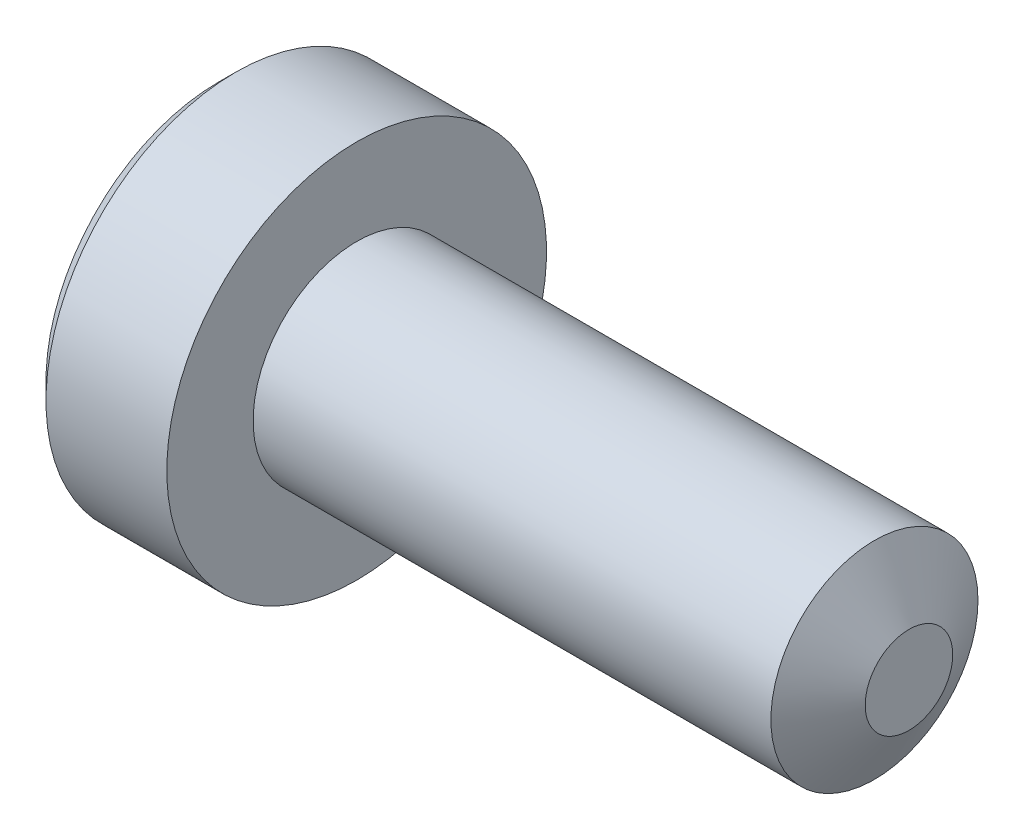
SolidWorks part; units mm, degrees
ref_plane "Front Plane" through (0, 0, 0) normal (0, 0, 1) x (1, 0, 0)
ref_plane "Top Plane" through (0, 0, 0) normal (0, 1, 0) x (1, 0, 0)
ref_plane "Right Plane" through (0, 0, 0) normal (1, 0, 0) x (0, 0, -1)
sketch "Sketch1" plane through (0, 0, 0) normal (0, 0, 1) x (1, 0, 0)
  line L0 (4, 0) -> (-4, 0) construction
  line L1 (4, 1.5) -> (4, -1.5) construction
  line L2 (-4, 2.75) -> (-4, -2.75) construction
  line L3 (-4, 2.75) -> (-5.75, 2.75) construction
  line L4 (-5.75, 2.75) -> (-6, 2.5) construction
  line L5 (-6, 2.5) -> (-6, -2.5) construction
  line L6 (-6, -2.5) -> (-5.75, -2.75) construction
  line L7 (-5.75, -2.75) -> (-4, -2.75) construction
  point P7 (-4.38, 0)
  point P12 (2, -1.5)
  dimension "D1" = 45
  dimension "Dec." = 3
  dimension "Length" = 8
  dimension "Head Dia" = 5.5
  dimension "Head Height" = 2
  dimension "Hex Depth" = 1.62
  dimension "Chamfer" = 0.25
  dimension "D2" = 2
ref_plane "Plane1" through (4, 0, 0) normal (1, 0, 0) x (0, 0, -1)
ref_plane "Plane2" through (-6, 0, 0) normal (1, 0, 0) x (0, 0, -1)
sketch "Sketch2" plane through (4, 0, 0) normal (1, 0, 0) x (0, 0, -1)
  circle A0 centre (0, 0) radius 1.5
extrude "Boss-Extrude1" add sketch "Sketch2" against normal up to vertex (8 mm away) up to point (-4, 0, 0)
sketch "Sketch3" plane through (4, 0, 0) normal (1, 0, 0) x (0, 0, -1)
  circle A0 centre (0, 0) radius 1.5 construction
  circle A1 centre (0, 0) radius 1.5
curve "Helix/Spiral1" pitch 0.5 height 8.5 radius 1.5 centre (4, 0, 0) axis (-1, 0, 0) start towards (0, 1, 0) parameters "Pitch"=0.5
chamfer "Chamfer1" distance 0.375 angle 45 1 edges at (4, 0, -1.5)
sketch "Sketch5" plane through (0, 0, 0) normal (0, 0, 1) x (1, 0, 0)
  line L0 (3.7813, 1.5) -> (4.2188, 1.5)
  line L1 (4.2188, 1.5) -> (4.0313, 1.1752)
  line L2 (4.0313, 1.1752) -> (3.9688, 1.1752)
  line L3 (3.9688, 1.1752) -> (3.7813, 1.5)
  line L4 (4, 1.1752) -> (4, 1.5) construction
  line L5 (3.875, 1.3376) -> (4.125, 1.3376) construction
  dimension "D1" = 60
  dimension "D2" = 0.25
  dimension "D3" = 0.0625
sweep "Cut-Sweep1" cut profiles "Sketch5" path "Helix/Spiral1" align with end faces yes
sketch "Sketch4" plane through (-6, 0, 0) normal (1, 0, 0) x (0, 0, -1)
  line L0 (-2.75, 0.7937) -> (2.75, 0.7937) construction
  line L1 (0, 1.1547) -> (-1, 0.5774)
  line L2 (-1, 0.5774) -> (-1, -0.5774)
  line L3 (-1, -0.5774) -> (0, -1.1547)
  line L4 (0, -1.1547) -> (1, -0.5774)
  line L5 (1, -0.5774) -> (1, 0.5774)
  line L6 (1, 0.5774) -> (0, 1.1547)
  line L7 (0, 0) -> (0, 0.7937) construction
  circle A0 centre (0, 0) radius 1 construction
  dimension "Hex Size" = 2
  dimension "D1" = 5.5
  dimension "D2" = 0.7937
sketch "Sketch6" plane through (0, 0, 0) normal (0, 0, 1) x (1, 0, 0)
  line L0 (-5.75, 2.75) -> (-6, 2.5) construction
  line L1 (-4, 2.75) -> (-5.75, 2.75) construction
  line L2 (-4, 2.75) -> (-4, -2.75) construction
  line L3 (-6, 2.5) -> (-6, -2.5) construction
  line L4 (-5.75, 2.75) -> (-6, 2.5)
  line L5 (-4, 2.75) -> (-5.75, 2.75)
  line L6 (-4, 2.75) -> (-4, 0)
  line L7 (-6, 2.5) -> (-6, 0)
  line L8 (-4, 0) -> (-6, 0) construction
  line L9 (-4, 0) -> (-6, 0)
revolve "Revolve1" add sketch "Sketch6" angle 360 about L8
extrude "Cut-Extrude1" cut sketch "Sketch4" along normal up to vertex (1.62 mm away) up to point (-4.38, 0, 0)
sketch "Sketch8" plane through (-6, 0, 0) normal (-1, 0, 0) x (0, 0, 1)
  circle A1 centre (0, 0) radius 1.1547
extrude "Cut-Extrude2" cut sketch "Sketch8" against normal through all draft 45
sketch "Sketch9" plane through (4, 0, 0) normal (1, 0, 0) x (0, 0, -1)
  circle A0 centre (0, 0) radius 1.5
  dimension "D1" = 3
extrude "Boss-Extrude2" add sketch "Sketch9" against normal up to surface (8.38 mm away) up to face at (-4.38, 0, 0)
chamfer "Chamfer2" distance 0.5 angle 60 1 edges at (4, 0, -1.5) first distance on face at (-4, 0, -1.5)
equation "\"D3@Helix/Spiral1\" = \"Length@Sketch1\"+\"Pitch@Helix/Spiral1\""
equation "\"D3@Sketch5\" = \"Pitch@Helix/Spiral1\"*.125"
equation "\"D2@Sketch5\" = \"Pitch@Helix/Spiral1\"*.50"
equation "\"D1@Chamfer1\" = \"Pitch@Helix/Spiral1\"*.75"
equation "\"D2@Sketch1\" = \"Pitch@Helix/Spiral1\"*4"
equation "\"D1@Sketch4\" = \"Head Dia@Sketch1\""
equation "\"Chamfer@Sketch1\" = \"Head Height@Sketch1\"/8"
